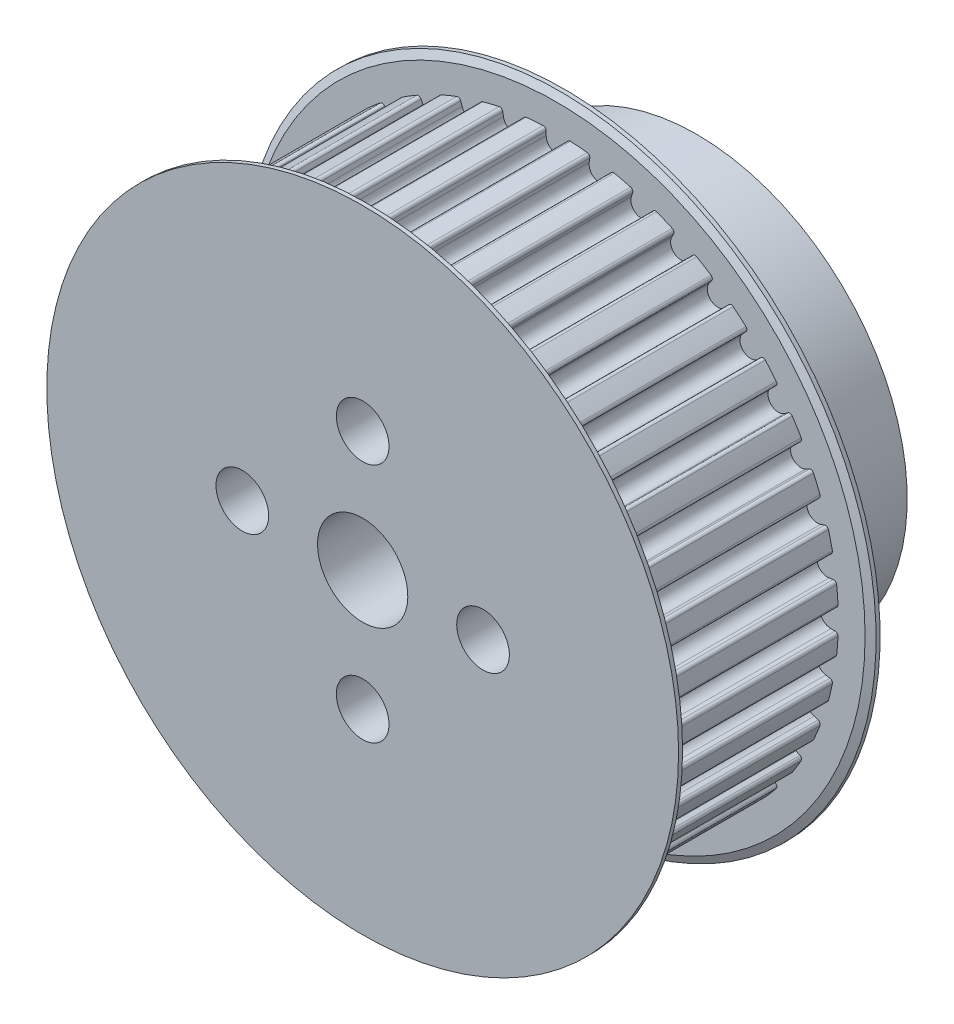
SolidWorks part; units mm, degrees
ref_plane "Front" through (0, 0, 0) normal (0, 0, 1) x (1, 0, 0)
ref_plane "Top" through (0, 0, 0) normal (0, 1, 0) x (1, 0, 0)
ref_plane "Right" through (0, 0, 0) normal (1, 0, 0) x (0, 0, -1)
sketch "support-front-body" plane through (0, 0, 0) normal (0, 0, 1) x (1, 0, 0)
  line L0 (0, 0) -> (0, 18.72) construction
  line L1 (0, 0) -> (0, -18.72) construction
  line L2 (0, 0) -> (18.72, 0) construction
  line L3 (0, 0) -> (-18.72, 0) construction
  circle A0 centre (0, 0) radius 18.72
  dimension "diam-outer" = 37.44
sketch "support-right-body" plane through (0, 0, 0) normal (1, 0, 0) x (0, 0, -1)
  line L0 (0, 0) -> (13.4, 0) construction
  line L1 (0, 18.72) -> (13.4, 18.72)
  line L2 (0, 18.72) -> (0, -18.72)
  line L3 (0, -18.72) -> (13.4, -18.72)
  line L4 (13.4, 18.72) -> (13.4, -18.72)
  dimension "length" = 13.4
sketch "support-right-chamfer" plane through (0, 0, 0) normal (1, 0, 0) x (0, 0, -1)
  line L0 (0, 0) -> (13.4, 0) construction
  line L1 (0, -18.72) -> (0, -17.72)
  line L2 (0, 18.72) -> (0, -18.72) construction
  line L4 (0, -17.72) -> (1, -18.72)
  line L5 (0, -18.72) -> (13.4, -18.72) construction
  line L7 (1, -18.72) -> (0, -18.72)
  line L9 (13.4, -18.72) -> (12.4, -18.72)
  line L11 (12.4, -18.72) -> (13.4, -17.72)
  line L12 (13.4, 18.72) -> (13.4, -18.72) construction
  line L14 (13.4, -17.72) -> (13.4, -18.72)
  dimension "height-chamfer-front" = 1
  dimension "angle-chamfer-front" = 45
  dimension "angle-chamfer-back" = 45
  dimension "height-chamfer-back" = 1
sketch "support-right-hub" plane through (0, 0, 0) normal (1, 0, 0) x (0, 0, -1)
  line L0 (22.2, 0) -> (13.4, 0) construction
  line L1 (13.4, 14) -> (22.2, 14)
  line L2 (13.4, 14) -> (13.4, -14)
  line L3 (13.4, -14) -> (22.2, -14)
  line L4 (22.2, 14) -> (22.2, -14)
  line L6 (0, 0) -> (13.4, 0) construction
  line L8 (0, 18.72) -> (0, -18.72) construction
  dimension "diam-hub" = 28
  dimension "length-hub" = 8.8
  dimension "dist-hub" = 13.4
sketch "support-right-bore" plane through (0, 0, 0) normal (1, 0, 0) x (0, 0, -1)
  line L0 (0, 18.72) -> (0, -18.72) construction
  line L1 (0, 3) -> (22.2, 3)
  line L2 (0, 3) -> (0, -3)
  line L3 (0, -3) -> (22.2, -3)
  line L4 (22.2, 3) -> (22.2, 0)
  line L5 (22.2, 0) -> (0, 0) construction
  line L6 (0, 0) -> (13.4, 0) construction
  line L7 (22.2, 0) -> (22.2, -3)
  line L8 (22.2, -3) -> (22.2, 3) construction
  dimension "diam-bore" = 6
  dimension "length-bore" = 22.2
  dimension "angle-bore-bottom" = 180
  dimension "angle-bore" = 90
sketch "support-stop-screw-hole" plane through (0, 0, 0) normal (1, 0, 0) x (0, 0, -1)
  line L1 (6.5667, 11) -> (9.4333, 11)
  line L2 (6.5667, 11) -> (6.5667, -1)
  line L3 (8, -1) -> (9.4333, -1)
  line L4 (9.4333, 11) -> (9.4333, -1)
  line L5 (8, -1) -> (8, 11) construction
  line L6 (8, -1) -> (6.5667, -1)
  line L7 (0, 0) -> (8, 0) construction
  line L8 (0, 18.72) -> (0, -18.72) construction
  dimension "diam-stop-screw-hole" = 2.8665
  dimension "dist-stop-screw-hole" = 8
  dimension "depth-stop-screw-hole" = 12
  dimension "angle-stop-screw-hole" = 180
  dimension "height-stop-screw-hole" = 11
sketch "support-front-keygroove" plane through (0, 0, 0) normal (0, 0, 1) x (1, 0, 0)
  line L0 (0, 0) -> (0, -3) construction
  line L1 (-1, 5) -> (1, 5)
  line L2 (-1, 5) -> (-1, 2.8)
  line L3 (-1, 2.8) -> (1, 2.8)
  line L4 (1, 5) -> (1, 2.8)
  line L5 (0, 0) -> (0, 3) construction
  circle A0 centre (0, 0) radius 3 construction
  dimension "width-keygroove" = 2
  dimension "dist-keygroove" = 8
  dimension "height-keygroove" = 2.2
sketch "support-front-tooth" plane through (0, 0, 0) normal (0, 0, 1) x (1, 0, 0)
  line L0 (0.7, 18.22) -> (0.7, 18.4981)
  line L1 (0, 0) -> (0, 18.72) construction
  line L2 (-0.7, 18.22) -> (-0.7, 18.4981)
  line L3 (0, 18.6979) -> (0, 18.72) construction
  line L8 (0, 18.6979) -> (0, 17.52) construction
  line L9 (0.9097, 18.6979) -> (-0.9097, 18.6979) construction
  line L10 (0, 18.6979) -> (0, 19.8758) construction
  line L17 (0.9097, 18.6979) -> (0.9097, 19.8758)
  line L21 (-0.9097, 19.8758) -> (-0.9097, 18.6979)
  line L22 (0.9097, 19.8758) -> (-0.9097, 19.8758)
  arc A0 (-0.7, 18.22) -> (0.7, 18.22) centre (0, 18.22) ccw
  circle A1 centre (0, 0) radius 18.72 construction
  arc A2 (0.7, 18.4981) -> (0.9097, 18.6979) centre (0.9, 18.4981) cw
  arc A3 (-0.7, 18.4981) -> (-0.9097, 18.6979) centre (-0.9, 18.4981) ccw
  circle A4 centre (0, 0) radius 18.72
  dimension "D3" = 0.2
  dimension "D2" = 0.7
  dimension "D1" = 1.2
sketch "support-right-flange" plane through (0, 0, 0) normal (1, 0, 0) x (0, 0, -1)
  line L0 (0, 9.3737) -> (0, 17.1246)
  line L1 (13.4, 18.72) -> (13.4, -18.72) construction
  line L2 (0, 17.1246) -> (0.5, 17.1246) construction
  line L3 (0.5, 17.1246) -> (0.5, 21)
  line L4 (0, 21) -> (0.5, 21)
  line L5 (0.5, 17.1246) -> (0.5, 9.3737)
  line L6 (0.5, 9.3737) -> (0, 9.3737)
  line L7 (6.7, 18.72) -> (6.7, 0) construction
  line L8 (0, 18.72) -> (13.4, 18.72) construction
  line L9 (0, 17.1246) -> (0, 21)
  line L10 (12.9, 9.3737) -> (13.4, 9.3737)
  line L11 (12.9, 17.1246) -> (12.9, 9.3737)
  line L12 (13.4, 21) -> (12.9, 21)
  line L13 (12.9, 17.1246) -> (12.9, 21)
  line L14 (13.4, 17.1246) -> (13.4, 21)
  line L15 (13.4, 9.3737) -> (13.4, 17.1246)
  line L16 (13.4, 0) -> (0, 0) construction
  line L17 (13.4, -9.3737) -> (13.4, -17.1246)
  line L18 (13.4, -17.1246) -> (13.4, -21)
  line L19 (12.9, -17.1246) -> (12.9, -21)
  line L20 (13.4, -21) -> (12.9, -21)
  line L21 (12.9, -17.1246) -> (12.9, -9.3737)
  line L22 (12.9, -9.3737) -> (13.4, -9.3737)
  line L23 (0.5, -9.3737) -> (0, -9.3737)
  line L24 (0.5, -17.1246) -> (0.5, -9.3737)
  line L25 (0, -21) -> (0.5, -21)
  line L26 (0.5, -17.1246) -> (0.5, -21)
  line L27 (0, -17.1246) -> (0, -21)
  line L28 (0, -9.3737) -> (0, -17.1246)
  line L29 (0, 0) -> (13.4, 0) construction
  line L30 (0, 17.1246) -> (0.5, 17.1246) construction
  line L31 (0.25, 9.3737) -> (0.25, 13.2492) construction
  line L32 (0.25, 13.2492) -> (0.25, 17.1246) construction
  line L33 (0.25, 21) -> (0.25, 17.1246) construction
  line L34 (0, 18.72) -> (13.4, 18.72) construction
  dimension "angle-flange" = 180
  dimension "thickness-flange" = 0.5
  dimension "diam-flange-inner" = 18.7475
  dimension "diam-flange-outer" = 42
  dimension "width-flange-inner" = 12.4
sketch "support-right-flange-profile" plane through (0, 0, 0) normal (1, 0, 0) x (0, 0, -1)
  line L0 (0.2668, 21) -> (0.5, 21)
  line L2 (0.5, 21) -> (0.5, 20.5)
  line L3 (0.5, 17.1246) -> (0.5, 9.3737) construction
  line L4 (0.5, 20.5) -> (0.2668, 21)
  line L5 (0, 0) -> (13.4, 0) construction
  line L6 (6.7, 0) -> (6.7, 18.72) construction
  line L7 (12.9, 20.5) -> (13.1332, 21)
  line L8 (12.9, 21) -> (12.9, 20.5)
  line L9 (13.1332, 21) -> (12.9, 21)
  dimension "D1" = 25
  dimension "D2" = 0.5
ref_axis "ref-axis-center" through (0, 0, -13.4) along (0, 0, 1)
ref_plane "ref-plane-front" through (0, 0, 0) normal (0, 0, 1) x (1, 0, 0)
ref_plane "ref-plane-back" through (0, 0, -13.4) normal (0, 0, 1) x (1, 0, 0)
ref_plane "ref-plane-hub-front" through (0, 0, -13.4) normal (0, 0, 1) x (1, 0, 0)
ref_plane "ref-plane-hub-back" through (0, 0, -22.2) normal (0, 0, 1) x (1, 0, 0)
ref_plane "ref-plane-bore-front" through (0, 0, 0) normal (0, 0, 1) x (1, 0, 0)
ref_plane "ref-plane-bore-back" through (0, 0, -22.2) normal (0, 0, 1) x (1, 0, 0)
ref_plane "ref-plane-stop-screw-hole-top" through (0, 11, 0) normal (0, 1, 0) x (-1, 0, 0)
ref_axis "ref-axis-stop-screw-hole" through (0, 11, -8) along (0, -1, 0)
sketch "Sketch5" plane through (0, 0, 0) normal (1, 0, 0) x (0, 0, -1)
  line L0 (13.4, 18.72) -> (13.4, -18.72) construction
  line L1 (0, 18.72) -> (13.4, 18.72) construction
  line L2 (0, 18.72) -> (0, -18.72) construction
  line L3 (0, 0) -> (13.4, 0) construction
  line L4 (13.4, 18.72) -> (13.4, 0)
  line L5 (0, 18.72) -> (13.4, 18.72)
  line L6 (0, 18.72) -> (0, 0)
  line L7 (0, 0) -> (13.4, 0) construction
  line L8 (0, 0) -> (13.4, 0)
revolve "body" add sketch "Sketch5" angle 360 about L7
sketch "Sketch11" plane through (0, 0, 0) normal (1, 0, 0) x (0, 0, -1)
  line L0 (0, -18.72) -> (0, -17.72) construction
  line L3 (1, -18.72) -> (0, -18.72) construction
  line L5 (0, -17.72) -> (1, -18.72) construction
  line L8 (0, -18.72) -> (0, -17.72)
  line L9 (1, -18.72) -> (0, -18.72)
  line L10 (0, -17.72) -> (1, -18.72)
  line L11 (0, 0) -> (13.4, 0) construction
  line L12 (0, 0) -> (13.4, 0) construction
revolve "cut-chamfer-front" [suppressed] cut sketch "Sketch11" angle 360 about L12
sketch "Sketch13" plane through (0, 0, 0) normal (1, 0, 0) x (0, 0, -1)
  line L0 (0, 0) -> (13.4, 0) construction
  line L1 (13.4, -18.72) -> (12.4, -18.72) construction
  line L2 (13.4, -17.72) -> (13.4, -18.72) construction
  line L3 (12.4, -18.72) -> (13.4, -17.72) construction
  line L4 (0, 0) -> (13.4, 0) construction
  line L5 (13.4, -18.72) -> (12.4, -18.72)
  line L6 (13.4, -17.72) -> (13.4, -18.72)
  line L7 (12.4, -18.72) -> (13.4, -17.72)
revolve "cut-chamfer-back" [suppressed] cut sketch "Sketch13" angle 360 about L4
sketch "Sketch16" plane through (0, 0, 0) normal (1, 0, 0) x (0, 0, -1)
  line L0 (22.2, 14) -> (22.2, -14) construction
  line L1 (13.4, 14) -> (22.2, 14) construction
  line L2 (22.2, 0) -> (13.4, 0) construction
  line L3 (13.4, 14) -> (13.4, -14) construction
  line L4 (22.2, 14) -> (22.2, 0)
  line L5 (13.4, 14) -> (22.2, 14)
  line L6 (22.2, 0) -> (13.4, 0) construction
  line L7 (13.4, 14) -> (13.4, 0)
  line L8 (22.2, 0) -> (13.4, 0)
revolve "body-hub" add sketch "Sketch16" angle 360 about L6
sketch "Sketch17" plane through (0, 0, 0) normal (1, 0, 0) x (0, 0, -1)
  line L0 (22.2, 3) -> (22.2, 0) construction
  line L1 (22.2, 0) -> (0, 0) construction
  line L2 (0, 3) -> (22.2, 3) construction
  line L3 (0, 3) -> (0, -3) construction
  line L4 (22.2, 3) -> (22.2, 0)
  line L5 (22.2, 0) -> (0, 0) construction
  line L6 (0, 3) -> (22.2, 3)
  line L7 (0, 3) -> (0, 0)
  line L8 (22.2, 0) -> (0, 0)
revolve "body-bore" cut sketch "Sketch17" angle 360 about L5
sketch "Sketch19" plane through (0, 0, 0) normal (1, 0, 0) x (0, 0, -1)
  line L0 (6.5667, 11) -> (9.4333, 11) construction
  line L1 (8, -1) -> (8, 11) construction
  line L2 (9.4333, 11) -> (9.4333, -1) construction
  line L3 (8, -1) -> (9.4333, -1) construction
  line L4 (8, 11) -> (9.4333, 11)
  line L5 (8, -1) -> (8, 11) construction
  line L6 (9.4333, 11) -> (9.4333, -1)
  line L7 (8, -1) -> (9.4333, -1)
  line L8 (8, -1) -> (8, 11)
revolve "body-stop-screw-hole" [suppressed] cut sketch "Sketch19" angle 360 about L5
pattern_circular "pattern-stop-screw-hole" [suppressed] count 2 every 90 about axis through (0, 0, -13.4) along (0, 0, 1) reverse direction yes
sketch "Sketch21" plane through (0, 0, 0) normal (0, 0, 1) x (1, 0, 0)
  line L0 (-1, 5) -> (1, 5) construction
  line L1 (-1, 5) -> (-1, 2.8) construction
  line L2 (-1, 2.8) -> (1, 2.8) construction
  line L3 (1, 5) -> (1, 2.8) construction
  line L4 (-1, 5) -> (1, 5)
  line L5 (-1, 5) -> (-1, 2.8)
  line L6 (-1, 2.8) -> (1, 2.8)
  line L7 (1, 5) -> (1, 2.8)
extrude "cut-keygroove" [suppressed] cut sketch "Sketch21" against normal up to surface (17.5 mm away)
sketch "Sketch23" plane through (0, 0, 0) normal (0, 0, 1) x (1, 0, 0)
  line L5 (0.7, 18.22) -> (0.7, 18.4981)
  line L6 (0.7, 18.22) -> (0.7, 18.4981)
  line L7 (-0.7, 18.4981) -> (-0.7, 18.22)
  line L8 (-0.7, 18.4981) -> (-0.7, 18.22)
  line L9 (0.9097, 18.6979) -> (0.9097, 19.8758)
  line L13 (-0.9097, 19.8758) -> (-0.9097, 18.6979)
  line L14 (0.9097, 19.8758) -> (-0.9097, 19.8758)
  line L15 (0.9097, 18.6979) -> (0.9097, 19.8758)
  line L19 (-0.9097, 19.8758) -> (-0.9097, 18.6979)
  line L20 (0.9097, 19.8758) -> (-0.9097, 19.8758)
  arc A3 (0.9097, 18.6979) -> (0.7, 18.4981) centre (0.9, 18.4981) ccw
  arc A4 (0.9097, 18.6979) -> (0.7, 18.4981) centre (0.9, 18.4981) ccw
  arc A5 (-0.7, 18.22) -> (0.7, 18.22) centre (0, 18.22) ccw
  arc A6 (-0.7, 18.22) -> (0.7, 18.22) centre (0, 18.22) ccw
  arc A7 (-0.7, 18.4981) -> (-0.9097, 18.6979) centre (-0.9, 18.4981) ccw
  arc A8 (-0.7, 18.4981) -> (-0.9097, 18.6979) centre (-0.9, 18.4981) ccw
  dimension "D1" = 0
extrude "cut-tooth" cut sketch "Sketch23" against normal up to surface (13.4 mm away) up to plane "ref-plane-back"
pattern_circular "pattern-tooth" count 40 over 360 about axis through (0, 0, -13.4) along (0, 0, 1) of "cut-tooth"
sketch "Sketch25" plane through (0, 0, 0) normal (1, 0, 0) x (0, 0, -1)
  line L0 (0, 0) -> (13.4, 0) construction
  line L1 (0.5, 9.3737) -> (0, 9.3737) construction
  line L2 (0.5, 17.1246) -> (0.5, 9.3737) construction
  line L4 (0, 21) -> (0.5, 21) construction
  line L5 (0, 17.1246) -> (0, 21) construction
  line L6 (0, 9.3737) -> (0, 17.1246) construction
  line L7 (0, 0) -> (13.4, 0) construction
  line L8 (0.5, 9.3737) -> (0, 9.3737)
  line L9 (0.5, 17.1246) -> (0.5, 9.3737)
  line L10 (0, 21) -> (0.5, 21)
  line L11 (0.5, 17.1246) -> (0.5, 21) construction
  line L12 (0, 17.1246) -> (0, 21)
  line L13 (0, 9.3737) -> (0, 17.1246)
  line L14 (0.5, 17.1246) -> (0.5, 21)
revolve "body-flange-front" add sketch "Sketch25" angle 360 about L7
sketch "Sketch26" plane through (0, 0, 0) normal (1, 0, 0) x (0, 0, -1)
  line L0 (13.4, 0) -> (0, 0) construction
  line L1 (12.9, 9.3737) -> (13.4, 9.3737) construction
  line L2 (12.9, 17.1246) -> (12.9, 9.3737) construction
  line L4 (13.4, 21) -> (12.9, 21) construction
  line L5 (13.4, 17.1246) -> (13.4, 21) construction
  line L6 (13.4, 9.3737) -> (13.4, 17.1246) construction
  line L7 (13.4, 0) -> (0, 0) construction
  line L8 (12.9, 9.3737) -> (13.4, 9.3737)
  line L9 (12.9, 17.1246) -> (12.9, 9.3737)
  line L10 (13.4, 21) -> (12.9, 21)
  line L11 (12.9, 17.1246) -> (12.9, 21) construction
  line L12 (13.4, 17.1246) -> (13.4, 21)
  line L13 (13.4, 9.3737) -> (13.4, 17.1246)
  line L14 (12.9, 17.1246) -> (12.9, 21)
revolve "body-flange-back" add sketch "Sketch26" angle 360 about L7
sketch "Sketch28" plane through (0, 0, 0) normal (1, 0, 0) x (0, 0, -1)
  line L0 (0.5, 21) -> (0.5, 20.5) construction
  line L1 (0.2668, 21) -> (0.5, 21) construction
  line L2 (0.5, 20.5) -> (0.2668, 21) construction
  line L3 (0.5, 21) -> (0.5, 20.5)
  line L4 (0.2668, 21) -> (0.5, 21)
  line L5 (0.5, 20.5) -> (0.2668, 21)
  line L6 (13.4, 0) -> (0, 0) construction
  line L7 (13.4, 0) -> (0, 0) construction
revolve "body-flange-profile-front" cut sketch "Sketch28" angle 360 about L7
sketch "Sketch29" plane through (0, 0, 0) normal (1, 0, 0) x (0, 0, -1)
  line L0 (13.4, 0) -> (0, 0) construction
  line L1 (12.9, 21) -> (12.9, 20.5) construction
  line L2 (13.1332, 21) -> (12.9, 21) construction
  line L3 (12.9, 20.5) -> (13.1332, 21) construction
  line L4 (13.4, 0) -> (0, 0) construction
  line L5 (12.9, 21) -> (12.9, 20.5)
  line L6 (13.1332, 21) -> (12.9, 21)
  line L7 (12.9, 20.5) -> (13.1332, 21)
revolve "body-flange-profile-back" cut sketch "Sketch29" angle 360 about L4
sketch "support-right-cut-body" plane through (0, 0, 0) normal (1, 0, 0) x (0, 0, -1)
  line L0 (13.4, 18.72) -> (13.4, -18.72) construction
  line L1 (0, 18.72) -> (13.4, 18.72) construction
  line L2 (0, 18.72) -> (0, -18.72) construction
  line L3 (0, -18.72) -> (13.4, -18.72) construction
  line L4 (13.4, 18.72) -> (13.4, -18.72) construction
  line L5 (0, 18.72) -> (0, -18.72) construction
  line L6 (0, 18.72) -> (13.4, 18.72) construction
  line L7 (0, -18.72) -> (13.4, -18.72) construction
  line L8 (13.4, 0) -> (0, 0) construction
  line L9 (6.7, 18.72) -> (6.7, -18.72) construction
  line L10 (13.4, 16.4867) -> (8.9333, 16.4867)
  line L11 (13.4, 16.4867) -> (13.4, -16.4867)
  line L12 (13.4, -16.4867) -> (8.9333, -16.4867)
  line L13 (8.9333, 16.4867) -> (8.9333, -16.4867)
  line L14 (0, 16.4867) -> (4.4667, 16.4867)
  line L15 (0, 16.4867) -> (0, -16.4867)
  line L16 (0, -16.4867) -> (4.4667, -16.4867)
  line L17 (4.4667, 16.4867) -> (4.4667, -16.4867)
  line L18 (8.9333, 16.4867) -> (4.4667, 16.4867) construction
  line L19 (4.4667, -16.4867) -> (6.7, -16.4867) construction
  line L20 (4.4667, -16.4867) -> (4.4667, -18.72) construction
  line L21 (13.4, 14) -> (8.9333, 14)
  line L23 (13.4, 14) -> (22.2, 14) construction
  line L24 (13.4, -14) -> (8.9333, -14)
  line L25 (0, 14) -> (4.4667, 14)
  line L26 (0, -14) -> (4.4667, -14)
sketch "Sketch31" plane through (0, 0, 0) normal (1, 0, 0) x (0, 0, -1)
  line L0 (0, 16.4867) -> (0, -16.4867) construction
  line L1 (0, 16.4867) -> (4.4667, 16.4867) construction
  line L2 (4.4667, 16.4867) -> (4.4667, -16.4867) construction
  line L3 (13.4, 16.4867) -> (13.4, -16.4867) construction
  line L4 (13.4, 16.4867) -> (8.9333, 16.4867) construction
  line L5 (8.9333, 16.4867) -> (8.9333, -16.4867) construction
  line L7 (0, 16.4867) -> (0, 14)
  line L8 (0, 16.4867) -> (4.4667, 16.4867)
  line L9 (4.4667, 16.4867) -> (4.4667, 14)
  line L10 (13.4, 16.4867) -> (13.4, 14)
  line L11 (13.4, 16.4867) -> (8.9333, 16.4867)
  line L12 (8.9333, 16.4867) -> (8.9333, 14)
  line L13 (13.4, 14) -> (8.9333, 14)
  line L14 (13.4, 14) -> (8.9333, 14) construction
  line L15 (4.4667, 14) -> (0, 14)
  line L16 (0, 0) -> (13.4, 0) construction
  line L17 (13.4, 0) -> (0, 0) construction
revolve "cut-body" [suppressed] cut sketch "Sketch31" angle 360 about L16
sketch "草图1" plane through (0, 0, 0) normal (0, 1, 0) x (1, 0, 0)
  line L0 (3, 22.2) -> (-3, 22.2) construction
  circle A0 centre (0, 17.7) radius 1.5
  dimension "D1" = 3
  dimension "D2" = 4.5
extrude "切除-拉伸1" cut sketch "草图1" against normal blind 23.5 contours A0
sketch "草图2" plane through (0, 0, -22.2) normal (0, 0, -1) x (-1, 0, 0)
  circle A0 centre (0, -8) radius 1.75
  circle A1 centre (0, 0) radius 3 construction
  circle A2 centre (-8, 0) radius 1.75
  circle A3 centre (0, 8) radius 1.75
  circle A4 centre (8, 0) radius 1.75
  point P13 (0, 0)
  dimension "D1" = 3.5
  dimension "D2" = 8
  dimension "D3" = 4
extrude "切除-拉伸2" cut sketch "草图2" against normal blind 39
